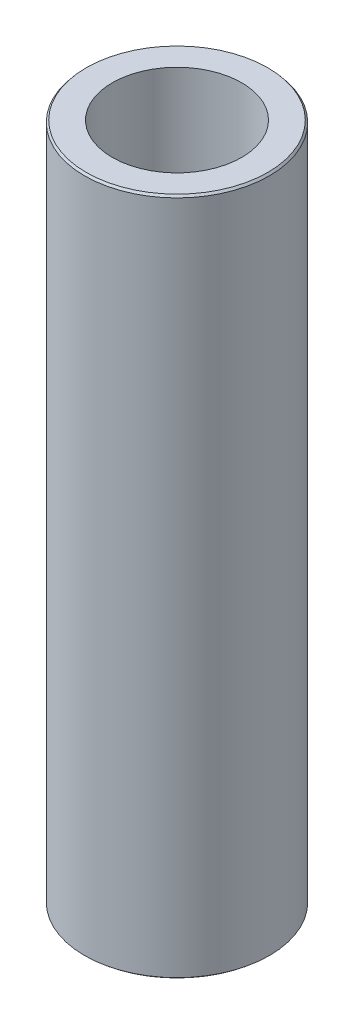
SolidWorks part; units mm, degrees
ref_plane "Front Plane" through (0, 0, 0) normal (0, 0, 1) x (1, 0, 0)
ref_plane "Top Plane" through (0, 0, 0) normal (0, 1, 0) x (1, 0, 0)
ref_plane "Right Plane" through (0, 0, 0) normal (1, 0, 0) x (0, 0, -1)
sketch "Sketch1" plane through (0, 0, 0) normal (0, 1, 0) x (1, 0, 0)
  circle A0 centre (0, 0) radius 60
  dimension "SHAFT_OD" = 120
extrude "Boss-Extrude1" add sketch "Sketch1" along normal blind 440.7229
sketch "Sketch2" plane through (0, 0, 0) normal (0, 1, 0) x (1, 0, 0)
  circle A0 centre (0, 0) radius 42.0025
  dimension "BORE_D" = 84.005
extrude "Cut-Extrude1" cut sketch "Sketch2" along normal through all
chamfer "Chamfer1" distance 1.3373 angle 39.804 2 edges at (0, 440.7229, 60) (0, 0, 60) first distance on face at (0, 440.7229, 60) first distance on face at (0, 0, 42.0025)
